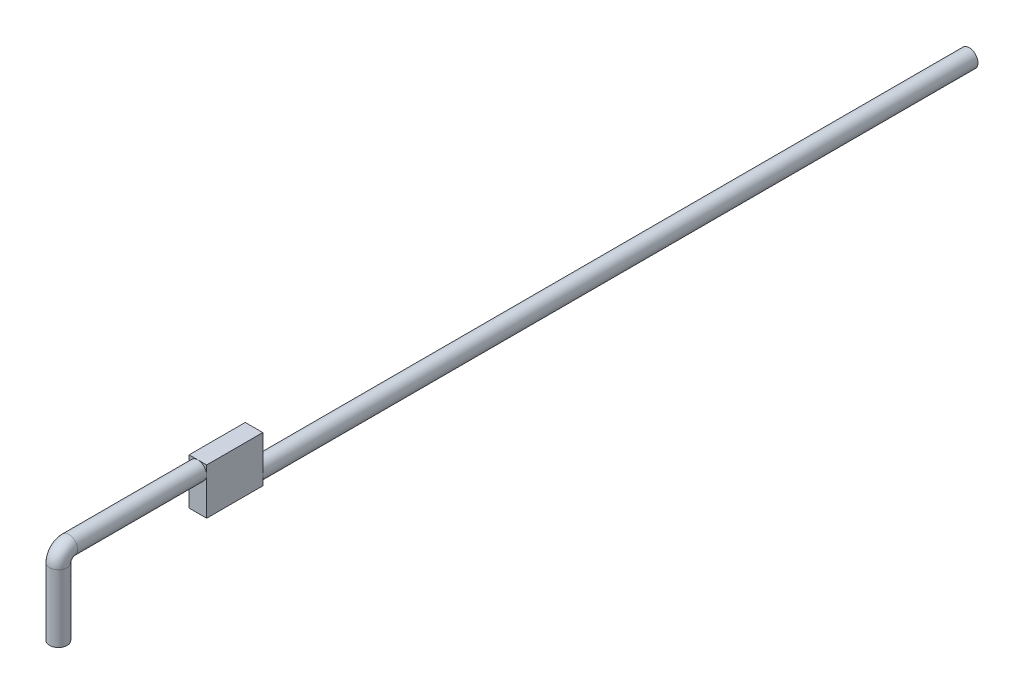
SolidWorks part; units mm, degrees
ref_plane "Front Plane" through (0, 0, 0) normal (0, 0, 1) x (1, 0, 0)
ref_plane "Top Plane" through (0, 0, 0) normal (0, 1, 0) x (1, 0, 0)
ref_plane "Right Plane" through (0, 0, 0) normal (1, 0, 0) x (0, 0, -1)
sketch "Sketch1" plane through (0, 0, 0) normal (0, 0, 1) x (1, 0, 0)
  circle A0 centre (0, 0) radius 1.9844
  dimension "D1" = 3.9688
extrude "Boss-Extrude1" add sketch "Sketch1" along normal blind 168.275
sketch "Sketch2" plane through (0, 0, 168.275) normal (0, 0, 1) x (1, 0, 0)
  line L1 (-1.9844, -1.9844) -> (1.9844, -1.9844)
  line L2 (-1.9844, -1.9844) -> (-1.9844, 8.4713)
  line L3 (-1.9844, 8.4713) -> (1.9844, 8.4713)
  line L4 (1.9844, -1.9844) -> (1.9844, 8.4713)
  circle A0 centre (0, 0) radius 1.9844 construction
extrude "Boss-Extrude2" add sketch "Sketch2" along normal blind 6.35 and the other way blind 6.35
sketch "Sketch3" plane through (0, 0, 174.625) normal (0, 0, 1) x (1, 0, 0)
  line L0 (1.9844, 8.4713) -> (-1.9844, 8.4713) construction
  circle A0 centre (0, 6.4869) radius 1.9844
  dimension "D1" = 3.9688
extrude "Boss-Extrude3" add sketch "Sketch3" along normal blind 29.21
sketch "Sketch4" plane through (0, 0, 203.835) normal (0, 0, 1) x (1, 0, 0)
  circle A0 centre (0, 6.4869) radius 1.9844
sketch "Sketch5" plane through (0, 0, 203.835) normal (0, 0, 1) x (1, 0, 0)
  line L0 (-5.9723, 4.113) -> (7.0862, 4.113) construction
revolve "Revolve5" add sketch "Sketch4" angle 90 about L0
sketch "Sketch6" plane through (0, 4.113, 0) normal (0, -1, 0) x (1, 0, 0)
  circle A0 centre (0, 206.2089) radius 1.9844
  circle A1 centre (0, 206.2089) radius 1.9844 construction
  point P2 (0, 0)
extrude "Boss-Extrude4" add sketch "Sketch6" along normal blind 15.24
